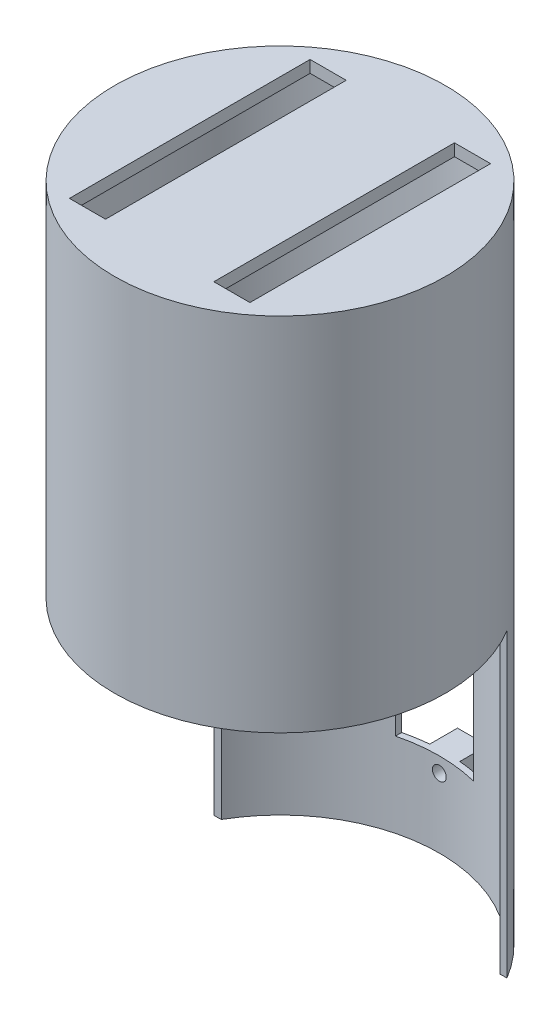
SolidWorks part; units mm, degrees
ref_plane "前基準面" through (0, 0, 0) normal (0, 0, 1) x (1, 0, 0)
ref_plane "上基準面" through (0, 0, 0) normal (0, 1, 0) x (1, 0, 0)
ref_plane "右基準面" through (0, 0, 0) normal (1, 0, 0) x (0, 0, -1)
sketch "草圖1" plane through (0, 0, 0) normal (0, 1, 0) x (1, 0, 0)
  circle A0 centre (0, 0) radius 27.5
  circle A1 centre (0, 0) radius 26.5
  dimension "D1" = 55
  dimension "D2" = 53
extrude "填料-伸長1" add sketch "草圖1" along normal blind 60 and the other way blind 50 contours A0
ref_plane "平面3" through (0, -10, 0) normal (0, 1, 0) x (1, 0, 0)
sketch "草圖8" plane through (0, 0, 0) normal (0, 1, 0) x (1, 0, 0)
  line L0 (0, 27.5) -> (0, -27.5) construction
  line L1 (14, 20.8205) -> (-14, 20.8205)
  line L2 (-14, 20.8205) -> (-14, -20.1795)
  line L3 (-14, -20.1795) -> (14, -20.1795)
  line L4 (14, 20.8205) -> (14, -20.1795)
  circle A1 centre (0, 0) radius 27.5 construction
  point P11 (0, -20.1795)
  point P12 (0, 20.8205)
  dimension "D1" = 28
  dimension "D2" = 41
sketch "草圖10" plane through (0, 60, 0) normal (0, 1, 0) x (1, 0, 0)
  line L0 (0, 27.5) -> (0, -27.5) construction
  line L1 (-15, 20) -> (-9, 20)
  line L2 (-15, 20) -> (-15, -20)
  line L3 (-15, -20) -> (-9, -20)
  line L4 (-9, 20) -> (-9, -20)
  line L5 (15, -20) -> (9, -20)
  line L6 (9, 20) -> (9, -20)
  line L7 (15, 20) -> (9, 20)
  line L8 (15, 20) -> (15, -20)
  line L9 (-15, -19.58) -> (-9, -19.58) construction
  line L10 (-27.5, 0) -> (27.5, 0) construction
  line L11 (-55, 0) -> (55, 0) construction
  circle A0 centre (0, 0) radius 27.5 construction
  dimension "D1" = 6
  dimension "D2" = 40
  dimension "D3" = 9
  dimension "D4" = 20
extrude "除料-伸長8" cut sketch "草圖10" against normal blind 8.1
ref_plane "平面4" through (0, 0, -37) normal (0, 0, 1) x (1, 0, 0)
extrude "除料-伸長9" cut sketch "草圖10<2>" against normal blind 10 and the other way blind 10
sketch "草圖10<2>" plane through (0, 60, 0) normal (0, 1, 0) x (1, 0, 0) same geometry as "草圖10"
sketch "草圖11" plane through (0, 0, 0) normal (0, 1, 0) x (1, 0, 0)
  line L0 (23.588, 14.1371) -> (-24.132, 13.1869)
  arc A0 (-24.132, 13.1869) -> (23.588, 14.1371) centre (0, 0) ccw
  circle A1 centre (0, 0) radius 27.5 construction
extrude "除料-伸長10" cut sketch "草圖11" against normal blind 54
sketch "草圖12" plane through (0, 0, 0) normal (0, 1, 0) x (1, 0, 0)
  line L0 (0, 27.5) -> (0, -27.5) construction
  circle A0 centre (0, 0) radius 26.5
  dimension "D1" = 53
extrude "除料-伸長11" cut sketch "草圖12" against normal blind 54 and the other way blind 58
sketch "草圖13" plane through (0, 0, 0) normal (0, 0, 1) x (1, 0, 0)
  line L0 (0, 0) -> (0, -54.6017) construction
  line L1 (-24.132, -25) -> (22.4286, -25) construction
  line L2 (-24.132, -50) -> (-24.132, 0) construction
  line L3 (22.4286, -50) -> (22.4286, 0) construction
  line L5 (-6.5, -12.5) -> (6.5, -12.5)
  line L6 (-6.5, -12.5) -> (-6.5, -36)
  line L7 (-6.5, -36) -> (6.5, -36)
  line L8 (6.5, -12.5) -> (6.5, -36)
  dimension "D1" = 13
  dimension "D2" = 23.5
  dimension "D3" = 6.5
  dimension "D4" = 12.5
extrude "除料-伸長12" cut sketch "草圖13" against normal blind 54
ref_plane "平面5" through (0, 0, -28) normal (0, 0, 1) x (1, 0, 0)
sketch "草圖14" plane through (0, 0, -28) normal (0, 0, 1) x (1, 0, 0)
  line L0 (0, -12.5) -> (0, -38.2336) construction
  line L1 (-6.5, -12.5) -> (6.5, -12.5) construction
  line L7 (6.5, -24.25) -> (-6.5, -24.25) construction
  line L8 (6.5, -12.5) -> (6.5, -36) construction
  line L9 (-6.5, -36) -> (-6.5, -12.5) construction
  line L10 (2.5, -36) -> (-2.5, -36)
  line L11 (2.5, -7.5) -> (-2.5, -7.5)
  line L12 (2.5, -7.5) -> (2.5, -12.5)
  line L13 (2.5, -12.5) -> (-2.5, -12.5)
  line L14 (-2.5, -7.5) -> (-2.5, -12.5)
  line L15 (-2.5, -41) -> (-2.5, -36)
  line L16 (2.5, -41) -> (-2.5, -41)
  line L17 (2.5, -41) -> (2.5, -36)
  dimension "D1" = 5
  dimension "D2" = 5
  dimension "D3" = 2.5
extrude "填料-伸長2" add sketch "草圖14" against normal blind 4 and the other way blind 1
sketch "草圖15" plane through (0, 0, -28) normal (0, 0, 1) x (1, 0, 0)
  line L0 (6.5, -24.25) -> (-6.5, -24.25) construction
  line L3 (6.5, -12.5) -> (6.5, -36) construction
  line L4 (-6.5, -36) -> (-6.5, -12.5) construction
  line L5 (30.25, -10) -> (-30.25, -10) construction
  circle A2 centre (0, -10) radius 1.15
  circle A3 centre (0, -38.5) radius 1.15
  dimension "D1" = 2.3
extrude "除料-伸長13" cut sketch "草圖15" against normal blind 5 and the other way blind 4
